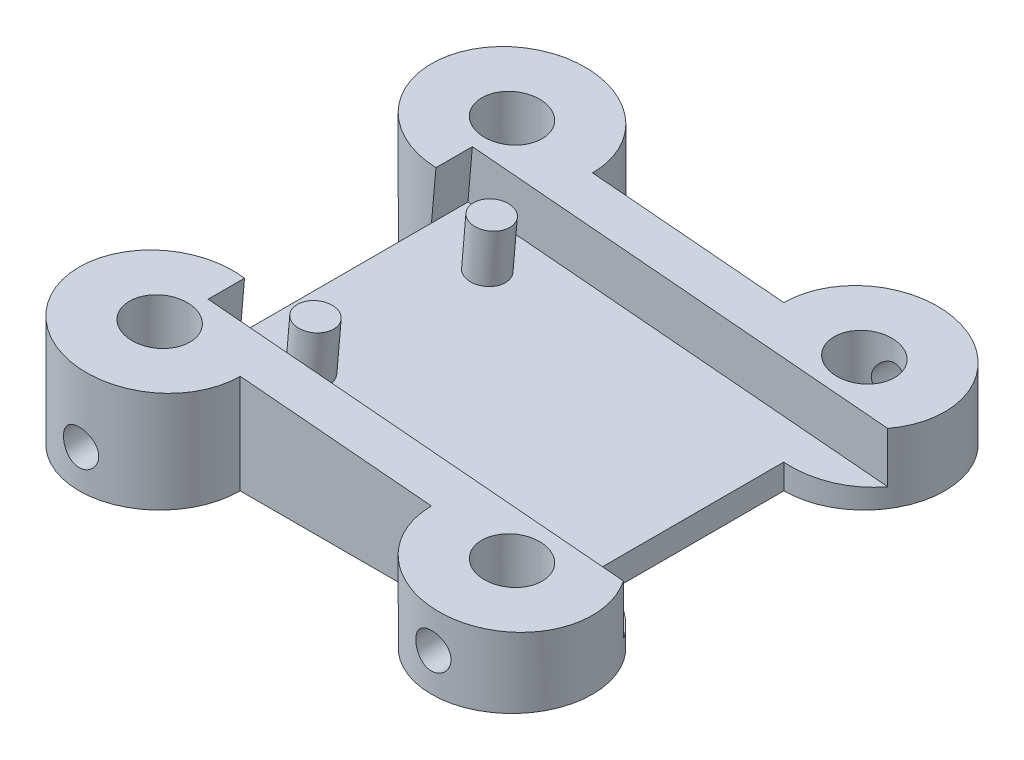
SolidWorks part; units mm, degrees
ref_plane "Front Plane" through (0, 0, 0) normal (0, 0, 1) x (1, 0, 0)
ref_plane "Top Plane" through (0, 0, 0) normal (0, 1, 0) x (1, 0, 0)
ref_plane "Right Plane" through (0, 0, 0) normal (1, 0, 0) x (0, 0, -1)
sketch "Sketch1" plane through (0, 0, 0) normal (0, 1, 0) x (1, 0, 0)
  line L0 (14, 28) -> (14, 0) construction
  line L1 (0, 0) -> (28, 0)
  line L2 (0, 0) -> (0, 28)
  line L3 (0, 28) -> (28, 28)
  line L4 (28, 0) -> (28, 28)
  line L5 (0, 14) -> (28, 14) construction
  point P9 (14, 14)
  dimension "D1" = 28
extrude "Boss-Extrude1" add sketch "Sketch1" along normal blind 8.4497
sketch "Sketch2" plane through (0, 0, 0) normal (0, 0, 1) x (1, 0, 0)
  line L0 (0, 8.4497) -> (28, 6)
  line L1 (0, 8.4497) -> (28, 8.4497) construction
  line L2 (28, 8.4497) -> (28, 0) construction
  line L3 (0, 8.4497) -> (28, 8.4497)
  line L4 (28, 8.4497) -> (28, 6)
  dimension "D2" = 6
  dimension "D3" = 5
extrude "Cut-Extrude1" cut sketch "Sketch2" against normal through all
sketch "Sketch3" plane through (0.7336, 8.3855, 0) normal (0.0872, 0.9962, 0) x (0.9962, -0.0872, 0)
  line L0 (-0.7364, 28) -> (-0.7364, 0) construction
  line L1 (-0.7364, 3.5) -> (49.2636, 3.5)
  line L2 (-0.7364, 3.5) -> (-0.7364, 24.5)
  line L3 (-0.7364, 24.5) -> (49.2636, 24.5)
  line L4 (49.2636, 3.5) -> (49.2636, 24.5)
  point P9 (-0.7364, 14)
  point P10 (-0.7364, 14)
  dimension "D1" = 21
  dimension "D2" = 50
extrude "Cut-Extrude2" cut sketch "Sketch3" against normal blind 4
ref_plane "Plane1" through (0, 8.4497, 0) normal (0, 1, 0) x (1, 0, 0)
sketch "Sketch11" plane through (0.385, 4.4007, 0) normal (0.0872, 0.9962, 0) x (0.9962, -0.0872, 0)
  line L0 (27.7205, 24.5) -> (-0.3865, 24.5) construction
  line L1 (27.7205, 24.5) -> (27.7205, 3.5) construction
  line L2 (-0.3865, 3.5) -> (27.7205, 3.5) construction
  line L3 (27.7205, 24.5) -> (-0.3865, 24.5) construction
  line L4 (27.7205, 24.5) -> (27.7205, 3.5) construction
  line L5 (-0.3865, 3.5) -> (27.7205, 3.5) construction
  line L6 (13.667, 3) -> (13.667, 50003) construction
  line L7 (24.633, 14) -> (-49975.367, 14) construction
  circle A2 centre (4.667, 21) radius 1.45
  circle A3 centre (4.667, 7) radius 1.45
  point P6 (13.667, 3.5)
  point P9 (27.7205, 14)
  dimension "D4" = 2.9
  dimension "D5" = 9
  dimension "D6" = 7
extrude "Boss-Extrude2" add sketch "Sketch11" along normal blind 4
sketch "Sketch12" plane through (0, 8.4497, 0) normal (0, 1, 0) x (1, 0, 0)
  line L0 (0, 3.5) -> (0, 24.5) construction
  line L1 (0, 3.5) -> (28, 3.5) construction
  line L2 (0, 3.5) -> (0, 24.5) construction
  line L3 (0, 3.5) -> (28, 3.5) construction
  line L4 (0, 14) -> (50000, 14) construction
  line L5 (14, 4) -> (14, 50004) construction
  circle A0 centre (14, 14) radius 7
  point P7 (0, 14)
  point P10 (14, 3.5)
  dimension "D1" = 14
sketch "Sketch13" plane through (0, 0, 0) normal (0, -1, 0) x (1, 0, 0)
  line L0 (0, 0) -> (28, 0) construction
  line L1 (28, 0) -> (28, -28) construction
  line L2 (28, -28) -> (0, -28) construction
  line L3 (0, -28) -> (0, 0) construction
  line L4 (0, 0) -> (28, 0) construction
  line L5 (28, 0) -> (28, -28) construction
  line L6 (28, -28) -> (0, -28) construction
  line L7 (0, -28) -> (0, 0) construction
  line L8 (0, -14) -> (28, -14) construction
  line L9 (14, -28) -> (14, 0) construction
  circle A0 centre (0, 0) radius 2.4
  circle A1 centre (28, 0) radius 2.4
  circle A2 centre (28, -28) radius 2.4
  circle A3 centre (0, -28) radius 2.4
  dimension "D1" = 4.8
  dimension "D2" = 2
  dimension "D3" = 2
extrude "Cut-Extrude5" cut sketch "Sketch13" against normal through all
sketch "Sketch14" plane through (0, 0, 0) normal (0, -1, 0) x (1, 0, 0)
  line L0 (28, -3.5) -> (28, -2.4) construction
  line L1 (2.4, -28) -> (25.6, -28) construction
  line L2 (0, -3.5) -> (0, -24.5) construction
  circle A0 centre (0, 0) radius 2.4 construction
  circle A1 centre (0, 0) radius 2.4 construction
  circle A2 centre (0, 0) radius 6.4
  circle A3 centre (0, 0) radius 2.4
  circle A4 centre (28, 0) radius 2.4
  circle A5 centre (28, 0) radius 6.4
  circle A6 centre (28, -28) radius 2.4
  circle A7 centre (28, -28) radius 6.4
  circle A8 centre (0, -28) radius 2.4
  circle A9 centre (0, -28) radius 6.4
  dimension "D1" = 4
  dimension "D4" = 4.8
  dimension "D2" = 2
  dimension "D3" = 2
extrude "Boss-Extrude3" add sketch "Sketch14" against normal up to surface (8.4497 mm away) up to face at (14, 7.2248, -25.8676)
sketch "Sketch15" plane through (0, 0, -28) normal (0, 0, -1) x (-1, 0, 0)
  line L0 (-21.6, 0) -> (-6.4, 0) construction
  line L1 (-21.9, 0) -> (-0.9, 0) construction
  line L4 (-14, 7.2248) -> (-14, 0) construction
  line L5 (-6.4, 7.8898) -> (-21.6, 6.5599) construction
  circle A0 centre (-28, 3) radius 1.4
  circle A1 centre (0, 3) radius 1.4
  point P4 (-28, 0)
  dimension "D1" = 2.8
  dimension "D2" = 3
extrude "Cut-Extrude6" cut sketch "Sketch15" along normal through all
sketch "Sketch16" plane through (0, 0, 0) normal (0, 0, 1) x (1, 0, 0)
  circle A0 centre (0, 3) radius 1.4 construction
  circle A1 centre (28, 3) radius 1.4 construction
  circle A2 centre (0, 3) radius 1.4
  circle A3 centre (28, 3) radius 1.4
extrude "Cut-Extrude7" cut sketch "Sketch16" along normal through all
sketch "Sketch18" plane through (0.7336, 8.3855, 0) normal (0.0872, 0.9962, 0) x (0.9962, -0.0872, 0)
  line L5 (-0.7364, 3.5) -> (27.157, 3.5) construction
  line L8 (4.6422, 3.5) -> (21.9919, 3.5) construction
  line L9 (4.6422, 3.5) -> (21.9919, 3.5) construction
  line L22 (4.9922, 24.5) -> (-0.3865, 24.5)
  line L37 (6.9919, 3.5) -> (36.9919, 3.5)
  line L38 (6.9919, 3.5) -> (6.9919, 24.5)
  line L39 (6.9919, 24.5) -> (36.9919, 24.5)
  line L40 (36.9919, 3.5) -> (36.9919, 24.5)
  line L42 (-0.3865, 24.5) -> (-0.3865, 21.6)
  line L46 (-0.3865, 6.4) -> (-0.3865, 3.5)
  line L47 (-0.3865, 3.5) -> (4.9922, 3.5)
  line L49 (4.6422, 24.5) -> (21.9919, 24.5) construction
  ellipse E1 centre (-0.3865, 28) end of major axis (6.038, 28) minor radius 6.4 (-0.3865, 21.6) -> (4.9922, 24.5) ccw construction
  ellipse E2 centre (-0.3865, 28) end of major axis (6.038, 28) minor radius 6.4 (-0.3865, 21.6) -> (4.9922, 24.5) ccw
  ellipse E3 centre (-0.3865, 0) end of major axis (6.038, 0) minor radius 6.4 (4.9922, 3.5) -> (-0.3865, 6.4) ccw construction
  ellipse E4 centre (-0.3865, 0) end of major axis (6.038, 0) minor radius 6.4 (4.9922, 3.5) -> (-0.3865, 6.4) ccw
  point P7 (21.9919, 3.5)
  dimension "D1" = 30
extrude "Cut-Extrude8" cut sketch "Sketch18" against normal up to surface (4 mm away) up to face at (6.4787, 3.8676, -21)
equation "\"TrackLength\"= 150"
equation "\"MarbleWidth\"= 13"
equation "\"MarbleTrackWidth\"= \"MarbleWidth\" - 1"
equation "\"TrackWidth\"= \"MarbleTrackWidth\" + ( 2 * 4 )"
equation "\"MarbleTrackLength\"= \"TrackLength\" - ( 2 * 8 )"
equation "\"MountWidth\"= \"TrackWidth\" + 8"
equation "\"D1@Sketch1\"=\"MountWidth\""
equation "\"D1@Boss-Extrude1\"=\"RampHeight\""
equation "\"RampDepth\"=6"
equation "\"RampAngle\"= 5"
equation "\"RampHeight\"= ( \"MountWidth\" * tan ( \"RampAngle\" ) ) + \"RampDepth\""
equation "\"D1@Sketch3\"=\"TrackWidth\" + 1"
equation "\"MountWidth\"= \"TrackWidth\" + 10"
equation "\"MountLength\"=66.6651"
